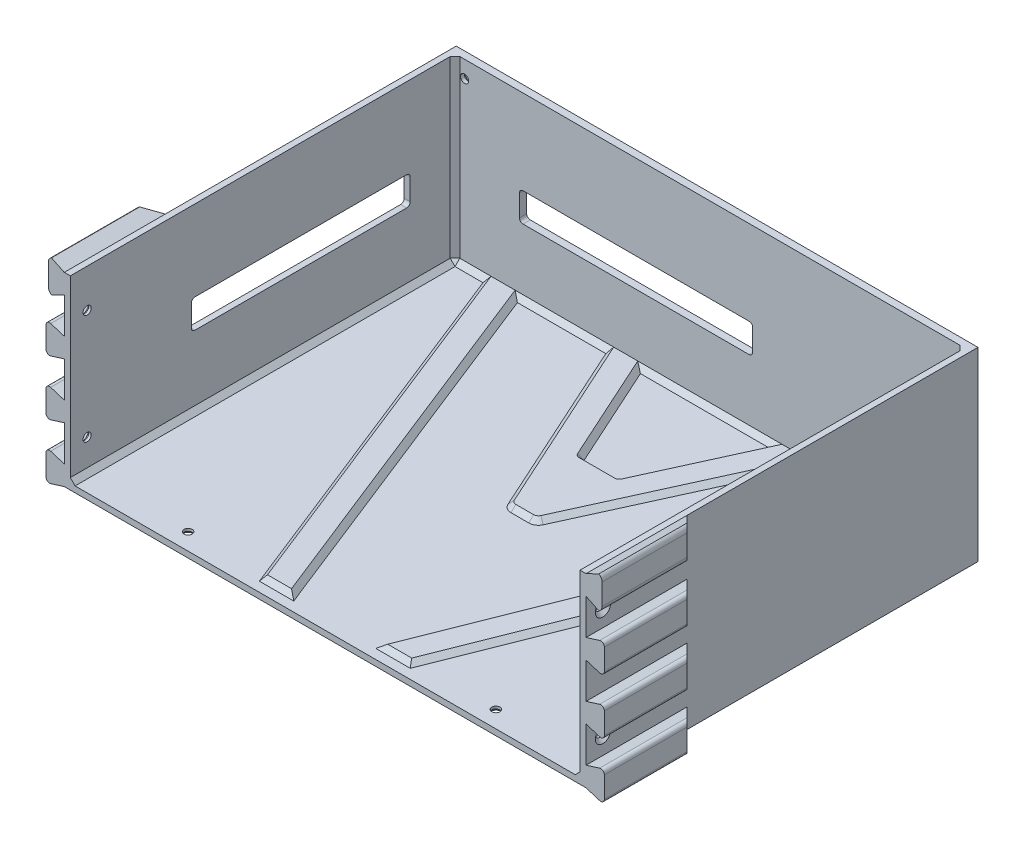
SolidWorks part; units mm, degrees
ref_plane "Płaszczyzna przednia" through (0, 0, 0) normal (0, 0, 1) x (1, 0, 0)
ref_plane "Płaszczyzna górna" through (0, 0, 0) normal (0, 1, 0) x (1, 0, 0)
ref_plane "Płaszczyzna prawa" through (0, 0, 0) normal (1, 0, 0) x (0, 0, -1)
sketch "Szkic1" plane through (0, 0, 0) normal (0, 0, 1) x (1, 0, 0)
  line L1 (0, 0) -> (217, 0)
  line L2 (0, 0) -> (0, 77.16)
  line L3 (0, 77.16) -> (217, 77.16)
  line L4 (217, 0) -> (217, 77.16)
  dimension "D1" = 77.16
  dimension "D2" = 217
extrude "Dodanie-wyciągnięcie1" add sketch "Szkic1" along normal blind 3
sketch "Szkic2" plane through (0, 0, 3) normal (0, 0, 1) x (1, 0, 0)
  line L0 (0, 77.16) -> (0, 0)
  line L1 (0, 0) -> (217, 0)
  line L2 (217, 0) -> (217, 77.16)
  line L3 (217, 77.16) -> (214.5, 77.16)
  line L4 (217, 77.16) -> (0, 77.16) construction
  line L5 (214.5, 77.16) -> (214.5, 2.5)
  line L6 (214.5, 2.5) -> (2.5, 2.5)
  line L7 (2.5, 2.5) -> (2.5, 77.16)
  line L8 (2.5, 77.16) -> (0, 77.16)
  dimension "D1" = 2.5
  dimension "D2" = 2.5
  dimension "D3" = 2.5
extrude "Dodanie-wyciągnięcie2" add sketch "Szkic2" along normal blind 160
sketch "Szkic3" plane through (0, 2.5, 0) normal (0, 1, 0) x (1, 0, 0)
  line L0 (17.5, -3) -> (78.5, -157)
  line L1 (214.5, -3) -> (2.5, -3) construction
  line L3 (27.5, -3) -> (88.5, -157)
  line L4 (214.5, -3) -> (2.5, -3) construction
  line L5 (101.1515, -50) -> (115.8485, -50)
  line L6 (78.5, -157) -> (88.5, -157)
  line L7 (17.5, -3) -> (27.5, -3)
  line L8 (199.5, -3) -> (138.5, -157)
  line L9 (138.5, -157) -> (128.5, -157)
  line L10 (128.5, -157) -> (138.5, -157)
  line L11 (128.5, -157) -> (189.5, -3)
  line L12 (189.5, -3) -> (199.5, -3)
  line L13 (217, 0) -> (0, 0) construction
  line L14 (68.5, -3) -> (102.9671, -78.8276)
  line L15 (114.0329, -78.8276) -> (148.5, -3)
  line L16 (138.5, -3) -> (117.6693, -48.8276)
  line L17 (99.3307, -48.8276) -> (78.5, -3)
  line L18 (104.7878, -80) -> (112.2122, -80)
  line L19 (68.5, -3) -> (78.5, -3)
  line L20 (138.5, -3) -> (148.5, -3)
  line L21 (108.5, 0) -> (108.5, -100) construction
  line L23 (214.5, -163) -> (2.5, -163) construction
  arc A0 (115.8485, -50) -> (117.6693, -48.8276) centre (115.8485, -48) ccw
  arc A1 (101.1515, -50) -> (99.3307, -48.8276) centre (101.1515, -48) cw
  arc A2 (112.2122, -80) -> (114.0329, -78.8276) centre (112.2122, -78) ccw
  arc A3 (104.7878, -80) -> (102.9671, -78.8276) centre (104.7878, -78) cw
  point P14 (108.5, 0)
  point P33 (113.5, -80)
  point P36 (103.5, -80)
  point P39 (108.5, -50)
  line M5 (214.5, -3) -> (2.5, -3)
  line M7 (2.5, -163) -> (214.5, -163)
  dimension "D16" = 2
  dimension "D1" = 20
  dimension "D2" = 15
  dimension "D3" = 40
  dimension "D4" = 10
  dimension "D5" = 15
  dimension "D6" = 10
  dimension "D7" = 10
  dimension "D8" = 10
  dimension "D9" = 10
  dimension "D10" = 10
  dimension "D11" = 10
  dimension "D12" = 5
  dimension "D13" = 60
  dimension "D14" = 80
  dimension "D15" = 30
  dimension "D17" = 6
extrude "Dodanie-wyciągnięcie3" add sketch "Szkic3" along normal blind 2 contours L3 L0 M5 M7 | L11 L8 M7 M5 | L20 L15 A2 L18 A3 L14 L19 L17 A1 L5 A0 L16 region at (53, 2.5, 80) region at (164, 2.5, 80)
chamfer "Sfazowanie2" distance 2 angle 45 25 edges at (169, 2.5, 80) (214.5, 39.83, 3) (214.5, 2.5, 83) (207, 2.5, 3) (58, 2.5, 80) (159, 2.5, 80) (169, 2.5, 3) (48, 2.5, 3) (48, 2.5, 80) (10, 2.5, 3) (2.5, 2.5, 83) (2.5, 39.83, 3) (108.5, 2.5, 3) (85.7335, 2.5, 40.9138) (103.7051, 2.5, 79.6815) (108.5, 2.5, 80) (113.2949, 2.5, 79.6815) (131.2665, 2.5, 40.9138) (128.0846, 2.5, 25.9138) (116.9313, 2.5, 49.6815) (108.5, 2.5, 50) (100.0687, 2.5, 49.6815) (88.9154, 2.5, 25.9138) (133.5, 2.5, 157) (83.5, 2.5, 157)
sketch "Szkic10" plane through (0, 0, 163) normal (0, 0, 1) x (1, 0, 0)
  line L0 (224.6, 87) -> (224.6, 0) construction
  line L1 (217, 0) -> (217, 77.16) construction
  line L2 (217, 0) -> (217, 8.16)
  line L3 (217, 0) -> (222.6526, -1.7665)
  line L4 (217, 8.16) -> (222.6526, 9.9265)
  line L5 (224.6, 8.4948) -> (224.6, -0.3348)
  line L6 (108.5, 77.16) -> (108.5, 114.4452) construction
  line L7 (212.5, 77.16) -> (4.5, 77.16) construction
  line L8 (217, 23) -> (217, 31.16)
  line L9 (217, 23) -> (222.6526, 21.2335)
  line L10 (217, 31.16) -> (222.6526, 32.9265)
  line L11 (224.6, 31.4948) -> (224.6, 22.6652)
  line L12 (217, 46) -> (217, 54.16)
  line L13 (217, 46) -> (222.6526, 44.2335)
  line L14 (217, 54.16) -> (222.6526, 55.9265)
  line L15 (224.6, 54.4948) -> (224.6, 45.6652)
  line L16 (-7.6, 54.4948) -> (-7.6, 45.6652)
  line L17 (0, 54.16) -> (-5.6526, 55.9265)
  line L18 (0, 46) -> (-5.6526, 44.2335)
  line L19 (0, 46) -> (0, 54.16)
  line L20 (-7.6, 31.4948) -> (-7.6, 22.6652)
  line L21 (0, 31.16) -> (-5.6526, 32.9265)
  line L22 (0, 23) -> (-5.6526, 21.2335)
  line L23 (0, 23) -> (0, 31.16)
  line L24 (-7.6, 8.4948) -> (-7.6, -0.3348)
  line L25 (0, 8.16) -> (-5.6526, 9.9265)
  line L26 (0, 0) -> (-5.6526, -1.7665)
  line L27 (0, 0) -> (0, 8.16)
  line L28 (217, 69) -> (217, 77.16)
  line L29 (217, 69) -> (222.3314, 66.4215)
  line L30 (217, 77.16) -> (222.3314, 79.7385)
  line L31 (223.6594, 77.4948) -> (223.6594, 68.6652)
  line L32 (-6.6594, 77.4948) -> (-6.6594, 68.6652)
  line L33 (0, 77.16) -> (-5.3314, 79.7385)
  line L34 (0, 69) -> (-5.3314, 66.4215)
  line L35 (0, 69) -> (0, 77.16)
  arc A0 (222.6526, -1.7665) -> (224.6, -0.3348) centre (223.1, -0.3348) ccw
  arc A1 (222.6526, 9.9265) -> (224.6, 8.4948) centre (223.1, 8.4948) cw
  arc A2 (222.6526, 21.2335) -> (224.6, 22.6652) centre (223.1, 22.6652) ccw
  arc A3 (222.6526, 32.9265) -> (224.6, 31.4948) centre (223.1, 31.4948) cw
  arc A4 (222.6526, 44.2335) -> (224.6, 45.6652) centre (223.1, 45.6652) ccw
  arc A5 (222.6526, 55.9265) -> (224.6, 54.4948) centre (223.1, 54.4948) cw
  arc A6 (-5.6526, 55.9265) -> (-7.6, 54.4948) centre (-6.1, 54.4948) ccw
  arc A7 (-5.6526, 44.2335) -> (-7.6, 45.6652) centre (-6.1, 45.6652) cw
  arc A8 (-5.6526, 32.9265) -> (-7.6, 31.4948) centre (-6.1, 31.4948) ccw
  arc A9 (-5.6526, 21.2335) -> (-7.6, 22.6652) centre (-6.1, 22.6652) cw
  arc A10 (-5.6526, 9.9265) -> (-7.6, 8.4948) centre (-6.1, 8.4948) ccw
  arc A11 (-5.6526, -1.7665) -> (-7.6, -0.3348) centre (-6.1, -0.3348) cw
  arc A12 (222.3314, 66.4215) -> (223.6594, 68.6652) centre (221.1, 68.6652) ccw
  arc A13 (222.3314, 79.7385) -> (223.6594, 77.4948) centre (221.1, 77.4948) cw
  arc A14 (-5.3314, 79.7385) -> (-6.6594, 77.4948) centre (-4.1, 77.4948) ccw
  arc A15 (-5.3314, 66.4215) -> (-6.6594, 68.6652) centre (-4.1, 68.6652) cw
  point P11 (224.6, -2.3751)
  point P14 (224.6, 10.5351)
  point P60 (-7.6, 10.5351)
  point P61 (-7.6, -2.3751)
  dimension "D5" = 1.5
  dimension "D1" = 7.6
  dimension "D2" = 8.16
  dimension "D3" = 23
  dimension "D4" = 34.71
  dimension "D6" = 3
extrude "Dodanie-wyciągnięcie6" add sketch "Szkic10" against normal blind 32
chamfer "Sfazowanie5" distance 10 angle 45 8 edges at (217, 50.08, 131) (217, 4.08, 131) (0, 4.08, 131) (0, 27.08, 131) (0, 50.08, 131) (217, 27.08, 131) (217, 73.08, 131) (0, 73.08, 131)
ref_plane "Płaszczyzna1" through (108.5, 0, 0) normal (-1, 0, 0) x (0, 0, 1)
sketch "Sketch1" plane through (0, 0, 0) normal (-1, 0, 0) x (0, 0, 1)
  line L4 (21.6472, 42.16) -> (21.6472, 33.16)
  line L5 (23.1472, 31.66) -> (111.1472, 31.66)
  line L6 (112.6472, 33.16) -> (112.6472, 42.16)
  line L7 (111.1472, 43.66) -> (23.1472, 43.66)
  line L8 (21.6472, 42.16) -> (21.6472, 33.16)
  line L9 (23.1472, 31.66) -> (111.1472, 31.66)
  line L10 (112.6472, 33.16) -> (112.6472, 42.16)
  line L11 (111.1472, 43.66) -> (23.1472, 43.66)
  arc A4 (23.1472, 43.66) -> (21.6472, 42.16) centre (23.1472, 42.16) ccw
  arc A5 (21.6472, 33.16) -> (23.1472, 31.66) centre (23.1472, 33.16) ccw
  arc A6 (111.1472, 31.66) -> (112.6472, 33.16) centre (111.1472, 33.16) ccw
  arc A7 (112.6472, 42.16) -> (111.1472, 43.66) centre (111.1472, 42.16) ccw
  arc A8 (23.1472, 43.66) -> (21.6472, 42.16) centre (23.1472, 42.16) ccw
  arc A9 (21.6472, 33.16) -> (23.1472, 31.66) centre (23.1472, 33.16) ccw
  arc A10 (111.1472, 31.66) -> (112.6472, 33.16) centre (111.1472, 33.16) ccw
  arc A11 (112.6472, 42.16) -> (111.1472, 43.66) centre (111.1472, 42.16) ccw
  dimension "D1" = 0
extrude "Cut-Extrude1" cut sketch "Sketch1" against normal up to next contours L9 A10 L10 A11 L11 A8 L8 A9
sketch "Sketch2" plane through (0, 0, 0) normal (0, 0, -1) x (-1, 0, 0)
  line L4 (-124.7972, 29.96) -> (-30.7972, 29.96)
  line L5 (-29.2972, 31.46) -> (-29.2972, 40.46)
  line L6 (-30.7972, 41.96) -> (-124.7972, 41.96)
  line L7 (-126.2972, 40.46) -> (-126.2972, 31.46)
  line L8 (-124.7972, 29.96) -> (-30.7972, 29.96)
  line L9 (-29.2972, 31.46) -> (-29.2972, 40.46)
  line L10 (-30.7972, 41.96) -> (-124.7972, 41.96)
  line L11 (-126.2972, 40.46) -> (-126.2972, 31.46)
  arc A4 (-126.2972, 31.46) -> (-124.7972, 29.96) centre (-124.7972, 31.46) ccw
  arc A5 (-30.7972, 29.96) -> (-29.2972, 31.46) centre (-30.7972, 31.46) ccw
  arc A6 (-29.2972, 40.46) -> (-30.7972, 41.96) centre (-30.7972, 40.46) ccw
  arc A7 (-124.7972, 41.96) -> (-126.2972, 40.46) centre (-124.7972, 40.46) ccw
  arc A8 (-126.2972, 31.46) -> (-124.7972, 29.96) centre (-124.7972, 31.46) ccw
  arc A9 (-30.7972, 29.96) -> (-29.2972, 31.46) centre (-30.7972, 31.46) ccw
  arc A10 (-29.2972, 40.46) -> (-30.7972, 41.96) centre (-30.7972, 40.46) ccw
  arc A11 (-124.7972, 41.96) -> (-126.2972, 40.46) centre (-124.7972, 40.46) ccw
  dimension "D1" = 0
extrude "Cut-Extrude2" cut sketch "Sketch2" against normal up to next contours L10 A11 L11 A8 L8 A9 L9 A10
sketch "Sketch3" plane through (217, 0, 0) normal (1, 0, 0) x (0, 0, -1)
  circle A0 centre (-156, 61.2082) radius 2 construction
  circle A1 centre (-156, 15.58) radius 2 construction
  circle A2 centre (-156, 61.2082) radius 2
  circle A3 centre (-156, 15.58) radius 2
sketch "Sketch4" plane through (0, 0, 0) normal (0, -1, 0) x (1, 0, 0)
  circle A0 centre (44.5, 156) radius 2 construction
  circle A1 centre (172.5, 156) radius 2 construction
  circle A3 centre (44.5, 156) radius 2
  circle A5 centre (172.5, 156) radius 2
  dimension "D1" = 4
sketch "Sketch5" plane through (0, 0, 0) normal (-1, 0, 0) x (0, 0, 1)
  circle A0 centre (156, 61.2082) radius 2 construction
  circle A1 centre (156, 15.58) radius 2 construction
  circle A2 centre (156, 61.2082) radius 2
  circle A3 centre (156, 15.58) radius 2
sketch "Sketch6" plane through (0, 0, 0) normal (-1, 0, 0) x (0, 0, 1)
  point P0 (156, 61.2082)
  point P3 (156, 15.58)
hole_wizard "CSK for M3 Countersunk Flat Head Screw1" positions "Sketch6" profile "Sketch7" countersink size "M3" standard "DIN" end condition up to next
sketch "Sketch7" plane through (0, 61.2082, 156) normal (0, 1, 0) x (0, 0, 1)
  line L0 (0, 0) -> (0, 2.5)
  line L1 (0, 2.5) -> (1.7, 2.5)
  line L2 (1.7, 2.5) -> (1.7, 1.45)
  line L3 (1.7, 1.45) -> (3.15, 0)
  line L5 (3.15, 0) -> (0, 0)
  line L6 (-1.7, 1.45) -> (-3.15, 0) construction
  line L11 (0, -6.35) -> (0, 107.95) construction
  dimension "Thru Hole Dia." = 3.4
  dimension "Thru Hole Depth" = 2.5
  dimension "Near C'Sink Dia." = 6.3
  dimension "Near C'Sink Angle" = 90
hole_wizard "CSK for M3 Countersunk Flat Head Screw2" positions "Sketch8" profile "Sketch9" countersink size "M3" standard "DIN" end condition up to next
sketch "Sketch8" plane through (0, 0, 0) normal (0, -1, 0) x (-1, 0, 0)
  point P0 (-44.5, -156)
  point P6 (-172.5, -156)
sketch "Sketch9" plane through (44.5, 0, 156) normal (1, 0, 0) x (0, 0, -1)
  line L0 (0, 0) -> (0, 2.5)
  line L1 (0, 2.5) -> (1.7, 2.5)
  line L2 (1.7, 2.5) -> (1.7, 1.45)
  line L3 (1.7, 1.45) -> (3.15, 0)
  line L5 (3.15, 0) -> (0, 0)
  line L6 (-1.7, 1.45) -> (-3.15, 0) construction
  line L11 (0, -6.35) -> (0, 107.95) construction
  dimension "Thru Hole Dia." = 3.4
  dimension "Thru Hole Depth" = 2.5
  dimension "Near C'Sink Dia." = 6.3
  dimension "Near C'Sink Angle" = 90
sketch "Sketch10" plane through (217, 0, 0) normal (1, 0, 0) x (0, 0, -1)
  point P0 (-156, 61.2082)
  point P3 (-156, 15.58)
hole_wizard "CSK for M3 Countersunk Flat Head Screw3" positions "Sketch10" profile "Sketch11" countersink size "M3" standard "DIN" end condition up to next
sketch "Sketch11" plane through (217, 61.2082, 156) normal (0, 1, 0) x (0, 0, -1)
  line L0 (0, 0) -> (0, 2.5)
  line L1 (0, 2.5) -> (1.7, 2.5)
  line L2 (1.7, 2.5) -> (1.7, 1.45)
  line L3 (1.7, 1.45) -> (3.15, 0)
  line L5 (3.15, 0) -> (0, 0)
  line L6 (-1.7, 1.45) -> (-3.15, 0) construction
  line L11 (0, -6.35) -> (0, 107.95) construction
  dimension "Thru Hole Dia." = 3.4
  dimension "Thru Hole Depth" = 2.5
  dimension "Near C'Sink Dia." = 6.3
  dimension "Near C'Sink Angle" = 90
sketch "Sketch12" plane through (0, 0, 0) normal (0, 0, -1) x (-1, 0, 0)
  circle A0 centre (-210.5, 70.16) radius 2 construction
  circle A1 centre (-6.5, 70.16) radius 2 construction
  circle A2 centre (-210.5, 70.16) radius 2
  circle A3 centre (-6.5, 70.16) radius 2
sketch "Sketch14" plane through (0, 0, 0) normal (0, 0, -1) x (-1, 0, 0)
  point P0 (-210.5, 70.16)
  point P3 (-6.5, 70.16)
hole_wizard "CSK for M3 Countersunk Flat Head Screw4" positions "Sketch14" profile "Sketch15" countersink size "M3" standard "DIN" end condition up to next
sketch "Sketch15" plane through (210.5, 70.16, 0) normal (1, 0, 0) x (0, 1, 0)
  line L0 (0, 0) -> (0, 3)
  line L1 (0, 3) -> (1.7, 3)
  line L2 (1.7, 3) -> (1.7, 1.45)
  line L3 (1.7, 1.45) -> (3.15, 0)
  line L5 (3.15, 0) -> (0, 0)
  line L6 (-1.7, 1.45) -> (-3.15, 0) construction
  line L11 (0, -6.35) -> (0, 107.95) construction
  dimension "Thru Hole Dia." = 3.4
  dimension "Thru Hole Depth" = 3
  dimension "Near C'Sink Dia." = 6.3
  dimension "Near C'Sink Angle" = 90
